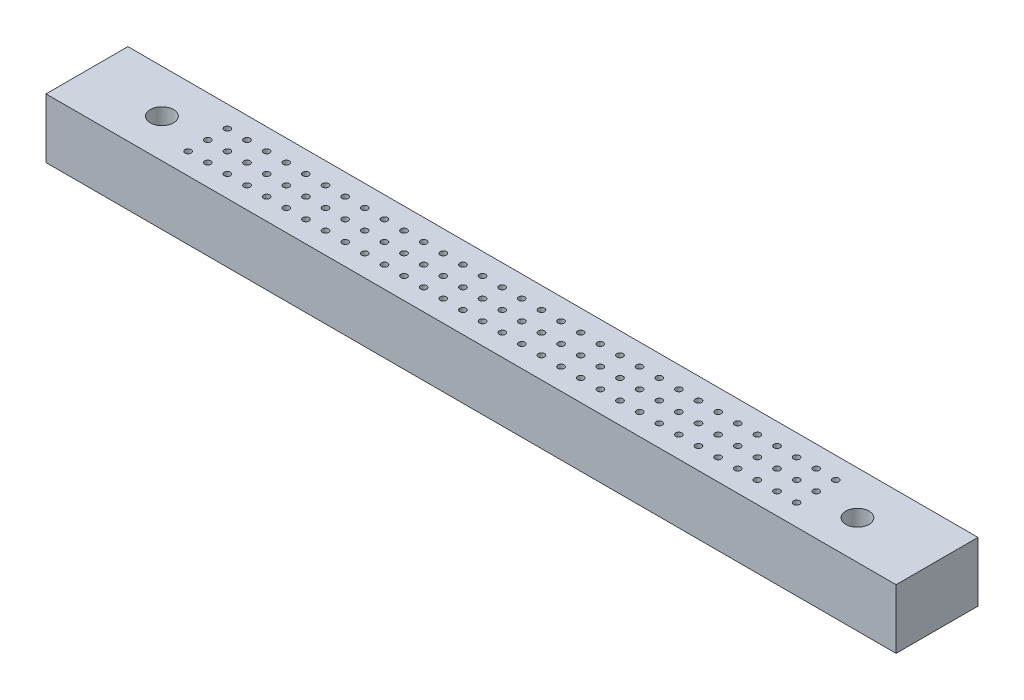
SolidWorks part; units mm, degrees
material "Polyetheretherketone (PEEK)"
ref_plane "Front Plane" through (0, 0, 0) normal (0, 0, 1) x (1, 0, 0)
ref_plane "Top Plane" through (0, 0, 0) normal (0, 1, 0) x (1, 0, 0)
ref_plane "Right Plane" through (0, 0, 0) normal (1, 0, 0) x (0, 0, -1)
sketch "Sketch1" plane through (0, 0, 0) normal (0, 1, 0) x (1, 0, 0)
  line L0 (-55, 0) -> (55, 0) construction
  line L1 (-55, -5) -> (55, -5)
  line L2 (-55, -5) -> (-55, 5)
  line L3 (-55, 5) -> (55, 5)
  line L4 (55, -5) -> (55, 5)
  line L5 (-55, -5) -> (55, 5) construction
  line L6 (-55, 5) -> (55, -5) construction
  line L7 (0, -55) -> (0, 55) construction
  circle A0 centre (45, 0) radius 1.5
  circle A1 centre (-45, 0) radius 1.5
  point P0 (0, 0)
  dimension "D4" = 3
  dimension "D1" = 10
  dimension "D2" = 110
  dimension "D3" = 45
extrude "Boss-Extrude1" add sketch "Sketch1" along normal blind 7.7
hole_wizard "Ø0.8 (0.8) Diameter Hole1" positions "3DSketch1" profile "Sketch3" hole size "Ø0.8" standard "ISO" end condition through all
sketch3d "3DSketch1"
  point P0 (-39.37, 7.7, -2.84)
  point P2 (-39.37, 7.7, -0.3)
  point P4 (-39.37, 7.7, 2.24)
  dimension "D4" = 0.3
  dimension "D1" = 2.54
  dimension "D2" = 2.54
  dimension "D3" = 39.37
sketch "Sketch3" plane through (-39.37, 7.7, -2.84) normal (1, 0, 0) x (0, 0, 1)
  line L0 (0, 0) -> (0, 7.7)
  line L1 (0, 7.7) -> (0.4, 7.7)
  line L2 (0.4, 7.7) -> (0.4, 0)
  line L5 (0.4, 0) -> (0, 0)
  line L11 (0, -6.35) -> (0, 107.95) construction
  dimension "Thru Hole Dia." = 0.8
  dimension "Thru Hole Depth" = 7.7
pattern_linear "LPattern1" count 32 spacing 2.54 along (1, 0, 0) of "Ø0.8 (0.8) Diameter Hole1"
sketch "Sketch6" plane through (0, 0, -5) normal (0, 0, -1) x (-1, 0, 0)
  line L1 (55, 0) -> (-55, 0)
  line L2 (55, 0) -> (55, 7.7)
  line L3 (55, 7.7) -> (-55, 7.7)
  line L4 (-55, 0) -> (-55, 7.7)
extrude "Boss-Extrude4" add sketch "Sketch6" along normal blind 0.6
ref_axis "Axis1" through (39.37, 0, -0.3) along (0, 1, 0)
ref_axis "Axis2" through (-39.37, 0, -0.3) along (0, 1, 0)
ref_plane "Plane2" through (0, 0, -0.3) normal (0, 0, -1) x (-1, 0, 0)
hole_wizard "Ø1.0mm Dowel Hole2" positions "3DSketch4" profile "Sketch9" hole size "Ø1.0" standard "ISO"
sketch3d "3DSketch4"
  point P0 (-50, 0, -0.3)
  point P2 (50, 0, -0.3)
  dimension "D1" = 50
  dimension "D2" = 50
sketch "Sketch9" plane through (-50, 0, -0.3) normal (1, 0, 0) x (0, 0, -1)
  line L0 (0, 0) -> (0, 4.3004)
  line L1 (0, 4.3004) -> (0.5, 4)
  line L2 (0.5, 4) -> (0.5, 0)
  line L5 (0.5, 0) -> (0, 0)
  line L10 (0, 4.3004) -> (-0.5, 4) construction
  line L11 (0, -6.35) -> (0, 107.95) construction
  dimension "Hole Dia." = 1
  dimension "Hole Depth" = 4
  dimension "Drill Angle" = 118
ref_plane "MidPlane 1" through (0, 0, -0.3) normal (0, 0, 1) x (1, 0, 0)
ref_plane "MidPlane 2" through (0, 0, 0) normal (-1, 0, 0) x (0, 0, 1)
